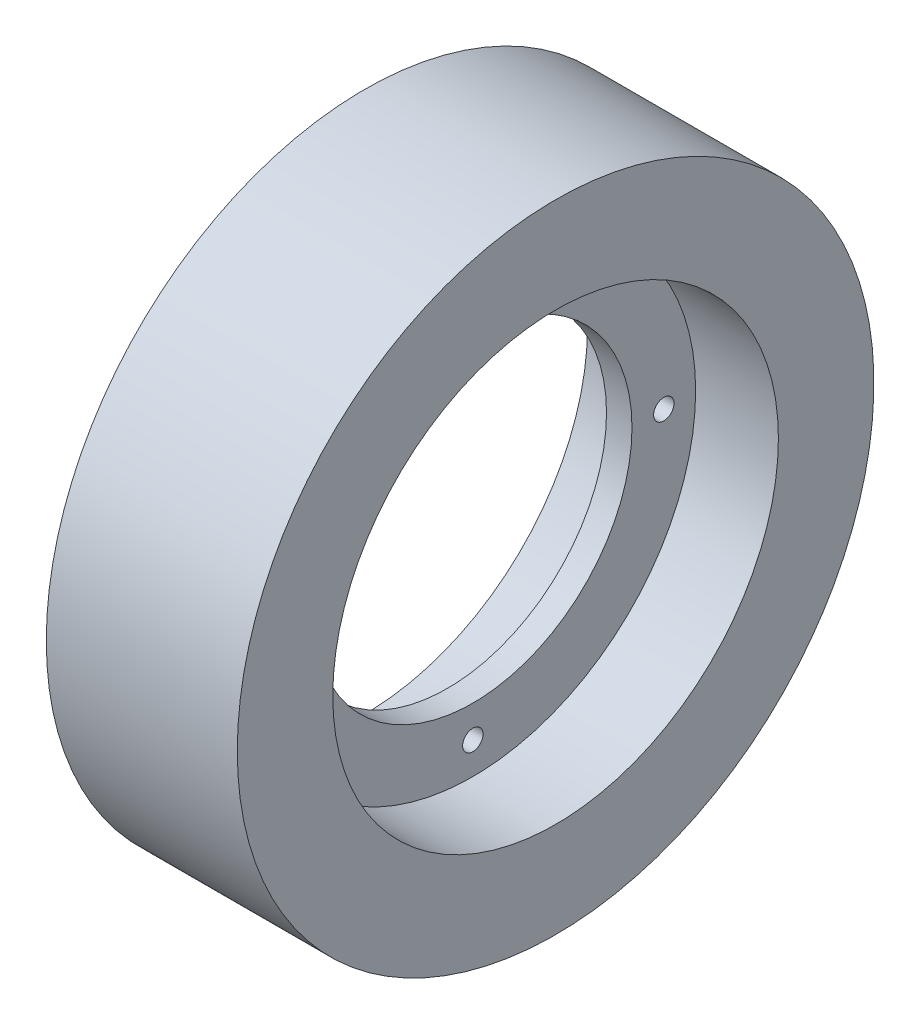
SolidWorks part; units mm, degrees
material "AISI 1020"
ref_plane "Front Plane" through (0, 0, 0) normal (0, 0, 1) x (1, 0, 0)
ref_plane "Top Plane" through (0, 0, 0) normal (0, 1, 0) x (1, 0, 0)
ref_plane "Right Plane" through (0, 0, 0) normal (1, 0, 0) x (0, 0, -1)
sketch "Sketch2" plane through (0, 0, 0) normal (0, 0, 1) x (1, 0, 0)
  line L0 (15, 50) -> (-15, 50)
  line L1 (15, 50) -> (15, 35)
  line L2 (15, 35) -> (2, 35)
  line L3 (2, 35) -> (2, 25)
  line L4 (2, 25) -> (-2, 25)
  line L5 (-2, 25) -> (-2, 35)
  line L6 (-2, 35) -> (-15, 35)
  line L7 (-15, 35) -> (-15, 50)
  line L8 (0, 0) -> (50000, 0) construction
  point P3 (0, 50)
  dimension "D1" = 30
  dimension "D2" = 50
  dimension "D3" = 13
  dimension "D4" = 35
  dimension "D5" = 25
revolve "Revolve1" add sketch "Sketch2" angle 360 about L8
sketch "Sketch3" plane through (2, 0, 0) normal (1, 0, 0) x (0, 0, -1)
  circle A0 centre (0, 30) radius 1.6
  circle A1 centre (0, 0) radius 30 construction
  dimension "D1" = 60
  dimension "D2" = 3.2
extrude "Cut-Extrude1" cut sketch "Sketch3" against normal through all
pattern_circular "CirPattern1" count 4 over 360 about axis through (2, 0, 0) along (-1, 0, 0) of "Cut-Extrude1"
